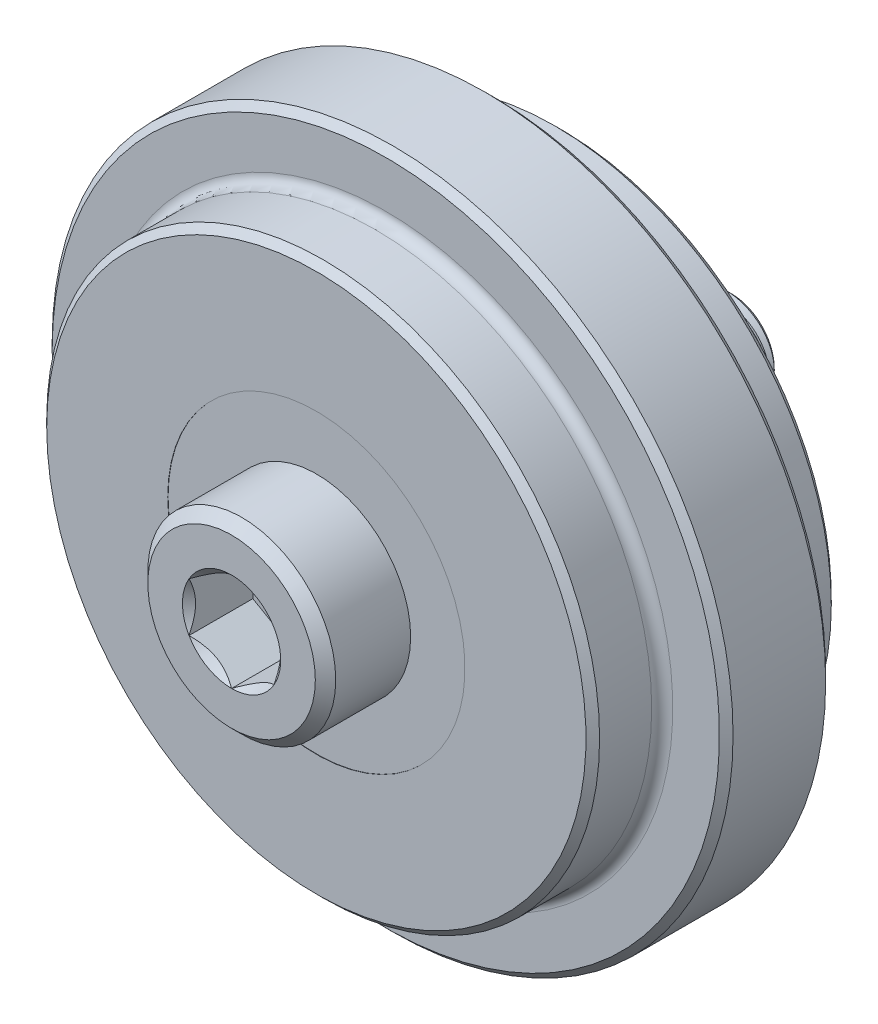
SolidWorks part; units mm, degrees
ref_plane "Front Plane" through (0, 0, 0) normal (0, 0, 1) x (1, 0, 0)
ref_plane "Top Plane" through (0, 0, 0) normal (0, 1, 0) x (1, 0, 0)
ref_plane "Right Plane" through (0, 0, 0) normal (1, 0, 0) x (0, 0, -1)
sketch "Sketch1" plane through (0, 0, 0) normal (1, 0, 0) x (0, 0, -1)
  line L0 (-2.0066, 9.525) -> (2.0066, 9.525)
  line L1 (-9.144, 11.0871) -> (-9.144, 20.1168)
  line L2 (9.144, 11.0871) -> (9.144, 20.1295)
  line L3 (-8.636, 20.6248) -> (-4.7498, 20.6248)
  line L4 (-3.9624, 21.4122) -> (-3.9624, 24.892)
  line L5 (-3.4544, 25.4) -> (3.4544, 25.4)
  line L6 (3.9624, 24.892) -> (3.9624, 21.4249)
  line L7 (4.7498, 20.6375) -> (8.636, 20.6375)
  line L8 (-9.144, 20.1168) -> (-8.636, 20.6248)
  line L9 (-3.9624, 24.892) -> (-3.4544, 25.4)
  line L10 (3.4544, 25.4) -> (3.9624, 24.892)
  line L11 (9.144, 0) -> (-9.144, 0) construction
  line L12 (8.636, 20.6375) -> (9.144, 20.1295)
  line L13 (-9.144, 11.0871) -> (-2.0066, 11.0871)
  line L14 (-2.0066, 11.0871) -> (-2.0066, 9.525)
  line L15 (2.0066, 9.525) -> (2.0066, 11.0871)
  line L16 (2.0066, 11.0871) -> (9.144, 11.0871)
  arc A0 (-4.7498, 20.6248) -> (-3.9624, 21.4122) centre (-4.7498, 21.4122) ccw
  arc A1 (3.9624, 21.4249) -> (4.7498, 20.6375) centre (4.7498, 21.4249) ccw
  dimension "D10" = 0.508
  dimension "D13" = 0.508
  dimension "D17" = 0.7874
  dimension "D18" = 0.7874
  dimension "D1" = 19.05
  dimension "D2" = 18.288
  dimension "D3" = 50.8
  dimension "D4" = 41.2496
  dimension "D5" = 41.275
  dimension "D6" = 7.9248
  dimension "D7" = 5.1816
  dimension "D8" = 5.1816
  dimension "D9" = 0.508
  dimension "D11" = 0.508
  dimension "D12" = 0.508
  dimension "D14" = 0.508
  dimension "D15" = 0.508
  dimension "D16" = 0.508
  dimension "D19" = 4.0132
  dimension "D20" = 7.1374
  dimension "D21" = 7.1374
  dimension "D22" = 22.1742
  dimension "D23" = 22.1742
revolve "Revolve1" add sketch "Sketch1" angle 360 mid plane about L11
sketch "Sketch2" plane through (0, 0, 0) normal (1, 0, 0) x (0, 0, -1)
  line L0 (-9.144, 0) -> (9.144, 0) construction
  line L1 (2.0066, 11.1125) -> (9.1186, 11.1125)
  line L2 (2.0066, 11.1125) -> (2.0066, 4.7879)
  line L3 (2.0066, 4.7879) -> (9.1186, 4.7879)
  line L4 (9.1186, 11.1125) -> (9.1186, 4.7879)
  line L5 (0, 0) -> (0, 11.1125) construction
  line L7 (2.0066, 9.525) -> (2.0066, 11.0871) construction
  line L8 (-9.1186, 11.1125) -> (-9.1186, 4.7879)
  line L9 (-2.0066, 4.7879) -> (-9.1186, 4.7879)
  line L10 (-2.0066, 11.1125) -> (-2.0066, 4.7879)
  line L11 (-2.0066, 11.1125) -> (-9.1186, 11.1125)
  dimension "D1" = 22.225
  dimension "D2" = 9.5758
  dimension "D3" = 7.112
revolve "Revolve2" add sketch "Sketch2" angle 360 mid plane about L0
sketch "Sketch3" plane through (0, 0, 0) normal (1, 0, 0) x (0, 0, -1)
  line L0 (-15.4686, 0) -> (21.8186, 0) construction
  line L1 (-15.4686, 0) -> (-15.4686, 6.2484)
  line L2 (-15.4686, 6.2484) -> (-14.7066, 7.0104)
  line L3 (-14.7066, 7.0104) -> (-9.1186, 7.0104)
  line L4 (-9.1186, 7.0104) -> (-9.1186, 4.7244)
  line L5 (-8.8646, 4.4704) -> (-7.0104, 4.4704)
  line L6 (-6.7564, 4.7244) -> (9.9314, 4.7244)
  line L7 (9.9314, 4.7244) -> (9.9314, 3.7338)
  line L8 (10.5664, 3.0988) -> (11.684, 3.0988)
  line L9 (11.938, 3.3528) -> (11.938, 3.9624)
  line L10 (11.938, 3.9624) -> (21.0566, 3.9624)
  line L11 (21.0566, 3.9624) -> (21.8186, 3.2004)
  line L12 (21.8186, 3.2004) -> (21.8186, 0)
  line L15 (-15.4686, 0) -> (21.8186, 0)
  line L16 (-9.1186, 11.1125) -> (-9.1186, 4.7879) construction
  arc A0 (-9.1186, 4.7244) -> (-8.8646, 4.4704) centre (-8.8646, 4.7244) ccw
  arc A1 (-7.0104, 4.4704) -> (-6.7564, 4.7244) centre (-7.0104, 4.7244) ccw
  arc A2 (9.9314, 3.7338) -> (10.5664, 3.0988) centre (10.5664, 3.7338) ccw
  arc A3 (11.684, 3.0988) -> (11.938, 3.3528) centre (11.684, 3.3528) ccw
  dimension "D15" = 0.254
  dimension "D16" = 0.635
  dimension "D17" = 0.254
  dimension "D1" = 6.35
  dimension "D2" = 30.9372
  dimension "D3" = 14.0208
  dimension "D4" = 0.762
  dimension "D5" = 0.762
  dimension "D6" = 7.9248
  dimension "D7" = 0.762
  dimension "D8" = 0.762
  dimension "D9" = 9.4488
  dimension "D10" = 6.1976
  dimension "D11" = 8.9408
  dimension "D12" = 9.8806
  dimension "D13" = 16.6878
  dimension "D14" = 2.3622
revolve "Revolve3" add sketch "Sketch3" angle 360 mid plane about L0
sketch "Sketch4" plane through (0, 0, -21.8186) normal (0, 0, -1) x (-1, 0, 0)
  circle A0 centre (0, 0) radius 3.9624
  point P3 (0, 3.9624)
curve "Helix/Spiral1" pitch 1.4111 height 11.2917 radius 3.9624 centre (0, 0, -21.8186) axis (0, 0, 1) start towards (0, 1, 0)
sketch "Sketch5" plane through (0, 0, 0) normal (1, 0, 0) x (0, 0, -1)
  line L0 (21.7304, 4.1152) -> (23.1415, 4.1152) construction
  line L1 (23.1415, 4.1152) -> (22.436, 2.8931) construction
  line L2 (22.436, 2.8931) -> (21.7304, 4.1152) construction
  line L3 (22.3478, 3.0459) -> (22.5242, 3.0459) construction
  line L4 (21.8186, 3.9624) -> (23.0533, 3.9624) construction
  line L5 (22.436, 2.8931) -> (22.436, 3.0459) construction
  line L6 (22.436, 3.9624) -> (22.436, 4.1152) construction
  line L7 (21.7745, 4.0388) -> (22.3172, 3.0988)
  line L8 (22.3172, 3.0988) -> (22.5547, 3.0988)
  line L9 (22.5547, 3.0988) -> (23.0974, 4.0388)
  line L10 (23.0974, 4.0388) -> (21.7745, 4.0388)
  line L11 (10.5664, 3.0988) -> (11.684, 3.0988) construction
  line L12 (22.436, 2.8931) -> (22.436, -3.9624) construction
  line L13 (22.436, -3.9624) -> (21.0249, -3.9624) construction
  line L14 (21.0249, -3.9624) -> (19.6137, -3.9624) construction
  line L15 (19.6137, -3.9624) -> (18.2026, -3.9624) construction
  line L17 (11.938, -3.9624) -> (21.0566, -3.9624) construction
  point P13 (22.436, 4.0388)
  dimension "D1" = 1.4111
  dimension "D2" = 0.1764
sweep "Cut-Sweep1" cut profiles "Sketch5" path "Helix/Spiral1" align with end faces yes
sketch "Sketch6" plane through (0, 0, 15.4686) normal (0, 0, 1) x (1, 0, 0)
  line L1 (0, 3.6662) -> (-3.175, 1.8331)
  line L2 (-3.175, 1.8331) -> (-3.175, -1.8331)
  line L3 (-3.175, -1.8331) -> (0, -3.6662)
  line L4 (0, -3.6662) -> (3.175, -1.8331)
  line L5 (3.175, -1.8331) -> (3.175, 1.8331)
  line L6 (3.175, 1.8331) -> (0, 3.6662)
  circle A0 centre (0, 0) radius 3.175 construction
  dimension "D1" = 6.35
extrude "Cut-Extrude1" cut sketch "Sketch6" against normal blind 4.7625
sketch "Sketch7" plane through (0, 0, 15.4686) normal (0, 0, 1) x (1, 0, 0)
  circle A0 centre (0, 0) radius 3.6662
extrude "Cut-Extrude2" cut sketch "Sketch7" against normal through all draft 45
sketch "Sketch8" plane through (0, 0, 0) normal (1, 0, 0) x (0, 0, -1)
  line L0 (-9.144, 0) -> (9.144, 0) construction
  line L1 (9.1186, 4.3815) -> (12.2936, 4.3815)
  line L2 (9.1186, 4.3815) -> (9.1186, 9.525)
  line L3 (9.1186, 9.525) -> (12.2936, 9.525)
  line L4 (12.2936, 4.3815) -> (12.2936, 9.525)
  line L5 (9.1186, 11.1125) -> (9.1186, 4.7879) construction
  dimension "D1" = 19.05
  dimension "D2" = 8.763
  dimension "D3" = 3.175
revolve "Revolve4" add sketch "Sketch8" angle 360 mid plane about L0
equation "\"D3@Helix/Spiral1\" = \"D4@Helix/Spiral1\" + \"D12@Sketch3\""
equation "\"D1@Sketch5\" = \"D4@Helix/Spiral1\""
equation "\"D2@Sketch5\" = \"D1@Sketch5\" / 8"
equation "\"D1@Cut-Extrude1\" = \"D1@Sketch6\" * 3 / 4"
